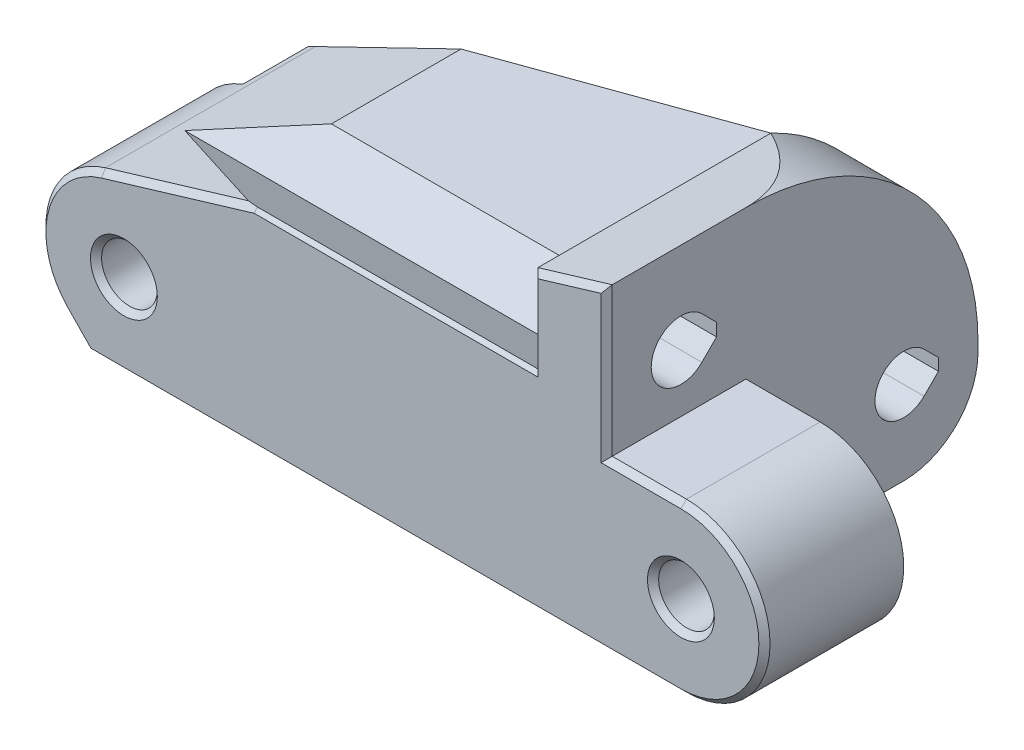
SolidWorks part; units mm, degrees
material "Custom Plastic"
ref_plane "Front Plane" through (0, 0, 0) normal (0, 0, 1) x (1, 0, 0)
ref_plane "Top Plane" through (0, 0, 0) normal (0, 1, 0) x (1, 0, 0)
ref_plane "Right Plane" through (0, 0, 0) normal (1, 0, 0) x (0, 0, -1)
sketch "Sketch1" plane through (0, 0, 0) normal (0, 0, 1) x (1, 0, 0)
  line L0 (0, 0) -> (24, 0) construction
  line L1 (26, 2) -> (24, 2) construction
  line L2 (26, 12.5) -> (-1.2933, 4.3101)
  line L3 (-3.2272, -3.1361) -> (-1.9018, -4.5)
  line L4 (26, 12.5) -> (26, 4.5)
  line L5 (24, 2) -> (24, -2) construction
  line L6 (24, -2) -> (26, -2) construction
  line L8 (-1.9018, -4.5) -> (30, -4.5)
  line L9 (30, 4.5) -> (26, 4.5)
  line L10 (26, 2) -> (26, -2) construction
  circle A0 centre (0, 0) radius 1.5
  arc A1 (-1.2933, 4.3101) -> (-3.2272, -3.1361) centre (0, 0) ccw
  circle A2 centre (30, 0) radius 1.5
  arc A3 (30, -4.5) -> (30, 4.5) centre (30, 0) ccw
  dimension "D1" = 3
  dimension "D6" = 3
  dimension "D2" = 4
  dimension "D3" = 4
  dimension "D4" = 2
  dimension "D5" = 30
extrude "Boss-Extrude1" add sketch "Sketch1" along normal blind 20
sketch "Sketch3" plane through (26, 0, 0) normal (1, 0, 0) x (0, 0, -1)
  line L0 (-16, 7.6) -> (-16, -7.6) construction
  line L1 (0, 0) -> (-16, 0) construction
  line L2 (-20, 4.5) -> (-20, 12.5) construction
  line L3 (-20, 12.5) -> (0, 12.5) construction
  circle A0 centre (-16, 7.6) radius 1.6
  circle A1 centre (-16, -7.6) radius 1.6 construction
  dimension "D1" = 3.2
  dimension "D2" = 4
  dimension "D3" = 4.9
extrude "Cut-Extrude3" cut sketch "Sketch3" against normal through all
sketch "Sketch4" plane through (0, 0, 0) normal (0, 0, -1) x (-1, 0, 0)
  line L0 (1.5877, 2.75) -> (1.5877, 5.8624)
  line L1 (-3.1754, 0) -> (-1.5877, -2.75)
  line L2 (-1.5877, -2.75) -> (1.5877, -2.75)
  line L3 (1.5877, -2.75) -> (3.1754, 0) construction
  line L4 (3.1754, 0) -> (1.5877, 2.75) construction
  line L5 (1.5877, 2.75) -> (-1.5877, 2.75)
  line L6 (-1.5877, 2.75) -> (-3.1754, 0)
  line L7 (1.5877, 5.8624) -> (6.5976, 5.8624)
  line L8 (6.5976, 5.8624) -> (6.5976, -6.0998)
  line L9 (6.5976, -6.0998) -> (1.5877, -6.0998)
  line L10 (1.5877, -6.0998) -> (1.5877, -2.75)
  line L11 (0, 0) -> (-30, 0) construction
  line L12 (-15, 0) -> (-15, 8.2903) construction
  circle A0 centre (0, 0) radius 2.75 construction
  dimension "D1" = 5.5
extrude "Cut-Extrude4" cut sketch "Sketch4" against normal blind 12
sketch "Sketch5" plane through (26, 0, 0) normal (1, 0, 0) x (0, 0, -1)
  line L0 (-13.3, 9.1588) -> (-20, 13.0271) construction
  line L1 (-20, 4.5) -> (-20, 12.5) construction
  line L2 (-13.3, 6.0412) -> (0, 6.0412)
  line L3 (-18.7, 10.5588) -> (-18.7, 7.4412) construction
  line L4 (-20, 6.7917) -> (-16, 4.4823)
  line L5 (-16, 4.4823) -> (-13.3, 6.0412)
  line L6 (-13.3, 6.0412) -> (-13.3, 9.1588) construction
  line L7 (0, 4.5) -> (0, 12.5) construction
  line L8 (0, 6.0412) -> (0, 12.5)
  line L9 (-20, 13.0271) -> (-20, 6.7917)
  line L10 (-20, 13.0271) -> (0, 12.5)
  line L11 (-13.3, 9.1588) -> (0, 12.5) construction
  line L13 (-16, 10.7177) -> (-19, 8.9856) [skipped]
  line L14 (-13.3, 9.1588) -> (-19, 12.4497) [skipped]
  circle A0 centre (-16, 7.6) radius 2.7 construction
  circle A1 centre (-16, 7.6) radius 1.6 construction
  arc A2 (-13.3, 6.0412) -> (-13.3, 9.1588) centre (-14.2, 7.6) ccw construction
  dimension "D1" = 5.4
extrude "Cut-Extrude5" cut sketch "Sketch5" against normal through all from offset 4 offset against normal yes
ref_plane "Plane1" through (0, 0, 7.5) normal (0, 0, 1) x (1, 0, 0)
sketch "Sketch11" plane through (0, 0, 0) normal (0, 1, 0) x (1, 0, 0)
  line L0 (22, 0) -> (-1.5877, -8.5)
  line L1 (-1.5877, -8.5) -> (-1.5877, 0)
  line L2 (-1.5877, 0) -> (22, 0)
  line L3 (-1.5877, 0) -> (-1.5877, -12) construction
  dimension "D1" = 8.5
extrude "Cut-Extrude11" cut sketch "Sketch11" against normal through all and the other way through all
sketch "Sketch10" plane through (0, 0, 7.5) normal (0, 0, 1) x (1, 0, 0)
  line L1 (26, 4.5) -> (35.1152, 4.5)
  line L2 (26, 4.5) -> (26, -4.926)
  line L3 (26, -4.926) -> (35.1152, -4.926)
  line L4 (35.1152, 4.5) -> (35.1152, -4.926)
extrude "Cut-Extrude10" cut sketch "Sketch10" along normal blind 5 and the other way through all
chamfer "Chamfer3" [suppressed] distance 6.5 angle 45
sketch "Sketch7" plane through (0, 0, 12.5) normal (0, 0, -1) x (-1, 0, 0)
  line L1 (-27.2, -1.6166) -> (-27.2, 1.6166)
  line L2 (-27.2, 1.6166) -> (-30, 3.2332)
  line L3 (-30, 3.2332) -> (-32.8, 1.6166)
  line L4 (-32.8, 1.6166) -> (-32.8, -1.6166)
  line L5 (-32.8, -1.6166) -> (-30, -3.2332)
  line L6 (-30, -3.2332) -> (-27.2, -1.6166)
  circle A0 centre (-30, 0) radius 2.8 construction
  circle A2 centre (-30, 0) radius 1.5 construction
  dimension "D1" = 5.6
extrude "Cut-Extrude7" cut sketch "Sketch7" against normal blind 4.5
sketch "Sketch8" plane through (22, 0, 0) normal (-1, 0, 0) x (0, 0, 1)
  line L0 (11.5, 0) -> (0, 0) construction
  line L1 (20, -3.1361) -> (20, 4.3101) construction
  line L2 (20, 12.5) -> (0, 12.5) construction
  line L3 (12.5, 0) -> (12.5, 12.5) construction
  line L4 (12.5, 12.5) -> (0, 12.5)
  line L5 (0, 12.5) -> (0, 0)
  circle A0 centre (4, 0) radius 1.55
  arc A1 (12.5, 12.5) -> (0, 0) centre (12.5, 0) ccw
  dimension "D1" = 3.1
  dimension "D2" = 16
extrude "Cut-Extrude8" cut sketch "Sketch8" against normal through all and the other way through all
fillet "Fillet1" radius 4 1 edges at (24, -4.5, 0)
sketch "Sketch9" plane through (22, 0, 0) normal (-1, 0, 0) x (0, 0, 1)
  circle A0 centre (4, 0) radius 3.5
  circle A2 centre (4, 0) radius 1.55 construction
  dimension "D1" = 7
extrude "Cut-Extrude9" cut sketch "Sketch9" along normal through all from offset 2
chamfer "Chamfer6" distance 1.8 angle 45 1 edges at (20, -1.55, 4)
sketch "Sketch12" plane through (26, 0, 0) normal (1, 0, 0) x (0, 0, -1)
  line L0 (-4, 0) -> (-2.904, -1.096)
  line L1 (-2.904, -1.096) -> (-2.13, -0.322)
  line L2 (-2.13, -0.322) -> (-2.13, 0.322)
  line L3 (-2.13, 0.322) -> (-2.904, 1.096)
  line L4 (-2.904, 1.096) -> (-4, 0)
  line L5 (-4, 0) -> (-2.13, 0) construction
  line L6 (-16, 7.6) -> (-14.8686, 6.4686)
  line L7 (-14.8686, 6.4686) -> (-14.08, 7.2573)
  line L8 (-14.08, 7.2573) -> (-14.08, 7.9427)
  line L9 (-14.08, 7.9427) -> (-14.8686, 8.7314)
  line L10 (-14.8686, 8.7314) -> (-16, 7.6)
  line L11 (-16, 7.6) -> (-14.08, 7.6) construction
  circle A0 centre (-4, 0) radius 1.55 construction
  circle A1 centre (-16, 7.6) radius 1.6 construction
  point P8 (-2.45, 0)
  point P10 (-14.4, 7.6)
  dimension "D1" = 0.32
  dimension "D2" = 0.32
extrude "Cut-Extrude12" cut sketch "Sketch12" against normal through all
chamfer "Chamfer7" distance 0.3 angle 45 12 edges at (31.5, 0, 20) (1.5, 0, 20) (22, 9.0457, 20) (24, 11.8999, 20) (26, 8.5, 20) (28, 4.5, 20) (34.5, 0, 20) (14.0491, -4.5, 20) (-2.5645, -3.8181, 20) (-4.3555, 1.1311, 20) (2.8417, 5.5509, 20) (14.4883, 6.7917, 20) first distance on face at (15.8959, 3.9101, 20)
